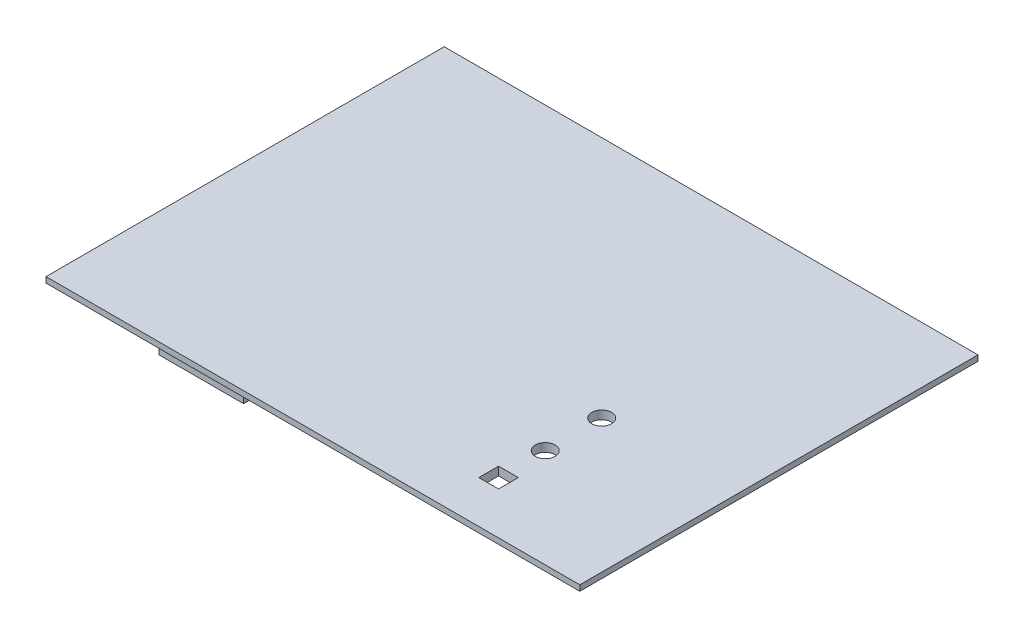
SolidWorks part; units mm, degrees
ref_plane "Plano frontal" through (0, 0, 0) normal (0, 0, 1) x (1, 0, 0)
ref_plane "Plano superior" through (0, 0, 0) normal (0, 1, 0) x (1, 0, 0)
ref_plane "Plano direito" through (0, 0, 0) normal (1, 0, 0) x (0, 0, -1)
sketch "Esboço1" plane through (0, 0, 0) normal (0, 1, 0) x (1, 0, 0)
  line L1 (-89.5, -65.5) -> (89.5, -65.5)
  line L2 (-89.5, -65.5) -> (-89.5, 65.5)
  line L3 (-89.5, 65.5) -> (89.5, 65.5)
  line L4 (89.5, -65.5) -> (89.5, 65.5)
  line L5 (-89.5, -65.5) -> (89.5, 65.5) construction
  line L6 (-89.5, 65.5) -> (89.5, -65.5) construction
  point P0 (0, 0)
  dimension "D1" = 179
  dimension "D2" = 131
extrude "Ressalto-extrusão1" add sketch "Esboço1" along normal blind 1
sketch "Esboço2" plane through (0, 1, 0) normal (0, 1, 0) x (1, 0, 0)
  line L1 (-94.5, -70.5) -> (94.5, -70.5)
  line L2 (-94.5, -70.5) -> (-94.5, 70.5)
  line L3 (-94.5, 70.5) -> (94.5, 70.5)
  line L4 (94.5, -70.5) -> (94.5, 70.5)
  line L5 (-94.5, -70.5) -> (94.5, 70.5) construction
  line L6 (-94.5, 70.5) -> (94.5, -70.5) construction
  point P0 (0, 0)
  dimension "D1" = 189
  dimension "D2" = 141
extrude "Ressalto-extrusão2" add sketch "Esboço2" along normal blind 2
sketch "Esboço3" plane through (0, 3, 0) normal (0, 1, 0) x (1, 0, 0)
  line L0 (0, 0) -> (0, -70.5) construction
  line L1 (-94.5, -70.5) -> (94.5, -70.5) construction
  line L2 (0, 0) -> (94.5, 0) construction
  line L3 (94.5, -70.5) -> (94.5, 70.5) construction
  line L4 (47.25, 0) -> (47.25, -70.5) construction
  line L5 (47.25, -35.25) -> (94.5, -35.25) construction
  line L7 (43.75, -55.5) -> (50.75, -55.5)
  line L8 (43.75, -55.5) -> (43.75, -48.5)
  line L9 (43.75, -48.5) -> (50.75, -48.5)
  line L10 (50.75, -55.5) -> (50.75, -48.5)
  line L11 (43.75, -55.5) -> (50.75, -48.5) construction
  line L12 (43.75, -48.5) -> (50.75, -55.5) construction
  circle A0 centre (47.25, -35.5) radius 3.5
  circle A1 centre (47.25, -15.5) radius 3.5
  point P16 (47.25, -52)
  dimension "D1" = 7
  dimension "D2" = 7
  dimension "D3" = 7
  dimension "D4" = 20
  dimension "D5" = 35
  dimension "D6" = 15
extrude "Corte-extrusão1" cut sketch "Esboço3" against normal through all
sketch "Esboço4" plane through (0, 3, 0) normal (0, 1, 0) x (1, 0, 0)
  line L0 (-64.5556, -60.5) -> (-34.5556, -60.5)
  line L1 (-34.5556, -60.5) -> (-34.5556, -58.5)
  line L2 (-34.5556, -58.5) -> (-64.5556, -58.5)
  line L3 (-64.5556, -58.5) -> (-64.5556, -60.5)
  line L4 (-64.5556, -15.5) -> (-34.5556, -15.5)
  line L5 (-34.5556, -15.5) -> (-34.5556, -17.5)
  line L6 (-34.5556, -17.5) -> (-64.5556, -17.5)
  line L7 (-64.5556, -17.5) -> (-64.5556, -15.5)
  line L8 (-94.5, -70.5) -> (94.5, -70.5) construction
  point P6 (-49.5556, -58.5)
  dimension "D1" = 2
  dimension "D2" = 30
  dimension "D3" = 41
  dimension "D4" = 10
extrude "Ressalto-extrusão3" add sketch "Esboço4" against normal blind 12
sketch "Esboço5" plane through (0, -9, 0) normal (0, -1, 0) x (1, 0, 0)
  line L0 (-64.5556, 60.5) -> (-64.5556, 54.5)
  line L1 (-64.5556, 54.5) -> (-34.5556, 54.5)
  line L2 (-34.5556, 54.5) -> (-34.5556, 60.5)
  line L3 (-34.5556, 60.5) -> (-64.5556, 60.5)
  line L4 (-64.5556, 15.5) -> (-64.5556, 21.5)
  line L5 (-64.5556, 21.5) -> (-34.5556, 21.5)
  line L6 (-34.5556, 21.5) -> (-34.5556, 15.5)
  line L7 (-34.5556, 15.5) -> (-64.5556, 15.5)
  dimension "D1" = 6
  dimension "D2" = 6
extrude "Ressalto-extrusão4" add sketch "Esboço5" along normal blind 2
